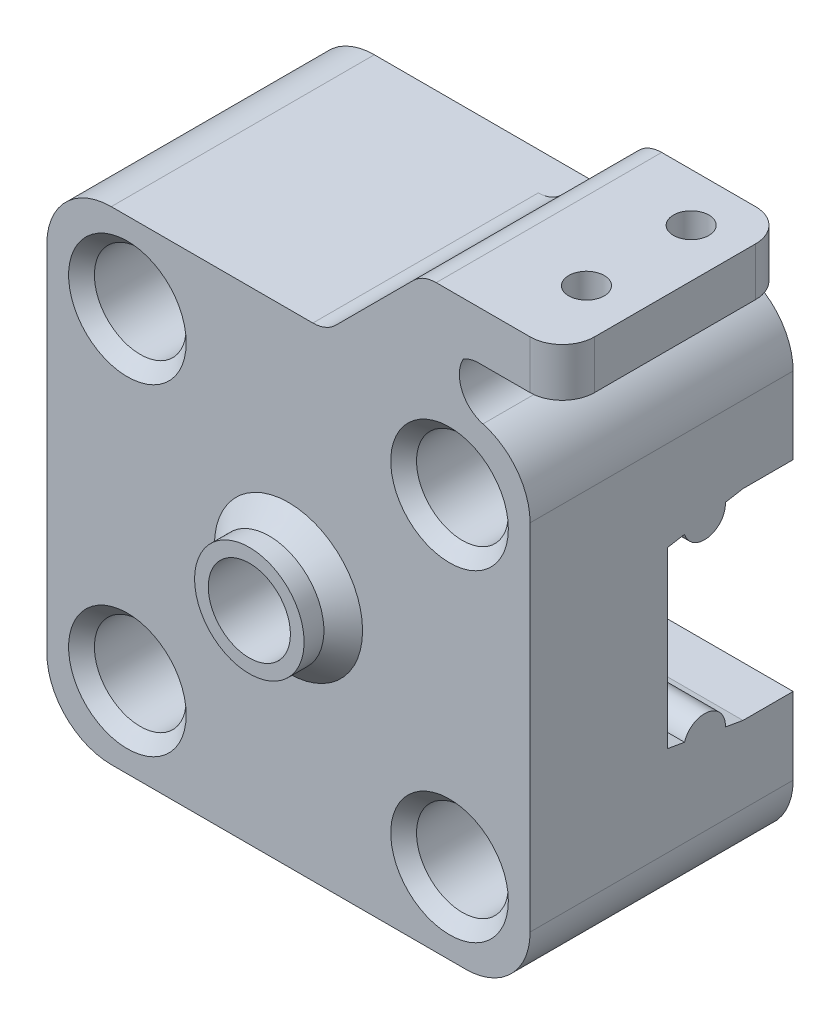
SolidWorks part; units mm, degrees
note: The reader was unsure of these and kept them because the rebuilt part matched: shared geometry of "Sketch1<3>".
ref_plane "Front Plane" through (0, 0, 0) normal (0, 0, 1) x (1, 0, 0)
ref_plane "Top Plane" through (0, 0, 0) normal (0, 1, 0) x (1, 0, 0)
ref_plane "Right Plane" through (0, 0, 0) normal (1, 0, 0) x (0, 0, -1)
sketch "Sketch1" plane through (0, 0, 0) normal (0, 0, 1) x (1, 0, 0)
  line L0 (10, 20) -> (10, 0) construction
  line L1 (0, 0) -> (20, 0) construction
  line L2 (0, 0) -> (0, 20) construction
  line L3 (0, 20) -> (20, 20) construction
  line L4 (20, 0) -> (20, 20) construction
  line L5 (10, 10) -> (68.0208, 10) construction
  line L6 (-5, -5) -> (25, -5)
  line L7 (-5, -5) -> (-5, 25)
  line L8 (-5, 25) -> (25, 25)
  line L9 (25, -5) -> (25, 25)
  line L10 (-5, -5) -> (25, 25) construction
  line L11 (-5, 25) -> (25, -5) construction
  line L13 (25, 16) -> (106.01, 16)
  line L14 (25, 16) -> (25, 4)
  line L15 (25, 4) -> (106.01, 4)
  line L16 (106.01, 16) -> (106.01, 4)
  circle A0 centre (0, 0) radius 1.6
  circle A1 centre (0, 20) radius 1.6
  circle A2 centre (20, 20) radius 1.6
  circle A3 centre (20, 0) radius 1.6
  point P11 (10, 10)
  dimension "D2" = 3.2
  dimension "D1" = 20
  dimension "D3" = 30
  dimension "D4" = 30
  dimension "D5" = 12
  dimension "D6" = 6
  dimension "D7" = 81.01
extrude "Boss-Extrude1" add sketch "Sketch1" along normal blind 6 contours L6 L9 L8 L7 A3 A2 A1 A0 | L16 L13 L9 L15
extrude "Boss-Extrude2" add sketch "Sketch1<3>" along normal blind 22.33 contours L6 L9 L8 L7 A3 A2 A1 A0
sketch "Sketch1<3>" plane through (0, 0, 0) normal (0, 0, 1) x (1, 0, 0) same geometry as "Sketch1"
sketch "Sketch2" plane through (25, 0, 0) normal (1, 0, 0) x (0, 0, -1)
  line L0 (-6.5176, 16.2291) -> (-9.1132, 16.2291)
  line L1 (-9.1132, 16.2291) -> (-10.2051, 16.0365)
  line L2 (-12.742, 15.5892) -> (-13.7853, 15.4053)
  line L3 (-13.7853, 15.4053) -> (-13.7853, 4.594)
  line L4 (-13.7853, 4.594) -> (-12.742, 4.41)
  line L5 (-10.2051, 3.9627) -> (-9.1132, 3.7702)
  line L6 (-9.1132, 3.7702) -> (-6.5176, 3.7702)
  line L7 (-6.5176, 3.7702) -> (-5.9631, 3.7702)
  line L9 (-5.9631, 16.2291) -> (-6.5176, 16.2291)
  line L11 (-22.33, -5) -> (0, -5) construction
  line L12 (-22.33, -5) -> (-22.33, 25) construction
  line L13 (-5.9631, 16.2291) -> (-5.9631, 3.7702)
  arc A0 (-12.742, 15.5892) -> (-10.2051, 16.0365) centre (-11.5012, 15.9695) ccw
  arc A1 (-10.2051, 3.9627) -> (-12.742, 4.41) centre (-11.5012, 4.0298) ccw
extrude "Cut-Extrude1" cut sketch "Sketch2" against normal through all
sketch "Sketch3" plane through (0, 0, 22.33) normal (0, 0, 1) x (1, 0, 0)
  line L0 (-5, 10) -> (25, 10) construction
  line L1 (-5, -5) -> (-5, 25) construction
  line L2 (25, -5) -> (25, 25) construction
  line L3 (10, -5) -> (10, 25) construction
  line L4 (-5, -5) -> (25, -5) construction
  line L5 (-5, 25) -> (25, 25) construction
  circle A0 centre (10, 10) radius 2.55
  dimension "D1" = 5.1
extrude "Cut-Extrude2" cut sketch "Sketch3" against normal blind 8
sketch "Sketch5" plane through (0, 0, 13.7853) normal (0, 0, -1) x (-1, 0, 0)
  line L1 (-5.3235, 10) -> (-7.6617, 14.05)
  line L2 (-7.6617, 14.05) -> (-12.3383, 14.05)
  line L3 (-12.3383, 14.05) -> (-14.6765, 10)
  line L4 (-14.6765, 10) -> (-12.3383, 5.95)
  line L5 (-12.3383, 5.95) -> (-7.6617, 5.95)
  line L6 (-7.6617, 5.95) -> (-5.3235, 10)
  line L8 (-25, 15.4053) -> (-25, 4.594)
  line L9 (-25, 4.594) -> (5, 4.594)
  line L10 (5, 4.594) -> (5, 15.4053)
  line L11 (5, 15.4053) -> (-25, 15.4053)
  line L12 (-25, 15.4053) -> (-25, 4.594)
  line L13 (-25, 4.594) -> (5, 4.594)
  line L15 (5, 15.4053) -> (-25, 15.4053)
  line L18 (5, 4.594) -> (5, 15.4053)
  circle A0 centre (-10, 10) radius 4.05
  circle A1 centre (-10, 10) radius 4.05 construction
  dimension "D2" = 8.1
  dimension "D3" = 8.1
  dimension "D1" = 0
extrude "Cut-Extrude3" cut sketch "Sketch5" against normal blind 4.5
sketch "Sketch6" plane through (0, 0, 0) normal (0, 0, -1) x (-1, 0, 0)
  line L0 (-20, 0) -> (0, 20) construction
  line L1 (0, 20) -> (0, 0) construction
  line L2 (0, 0) -> (-20, 20) construction
  circle A0 centre (-10, 10) radius 5
  dimension "D1" = 10
extrude "Cut-Extrude5" cut sketch "Sketch6" against normal blind 8.6
sketch "Sketch7" plane through (0, 0, 0) normal (0, 0, -1) x (-1, 0, 0)
  line L1 (5, -5) -> (-3.5, -5)
  line L2 (5, -5) -> (5, 25)
  line L3 (5, 25) -> (-3.5, 25)
  line L4 (-3.5, -5) -> (-3.5, 25)
  line L5 (5, 25) -> (-25, 25) construction
  line L6 (-106.01, 10) -> (-3.5, 10) construction
  line L7 (-106.01, 16) -> (-106.01, 4) construction
  line L8 (-3.5, 10) -> (-3.5, 16)
  line L9 (-25, 4) -> (-106.01, 4) construction
  line L10 (-3.5, 16) -> (-65, 16)
  line L11 (-3.5, 16) -> (-3.5, 4)
  line L12 (-3.5, 4) -> (-65, 4)
  line L13 (-65, 16) -> (-65, 4)
  circle A0 centre (-49.5, 10) radius 1.6
  circle A1 centre (-74.5, 10) radius 1.6
  circle A2 centre (-99.5, 10) radius 1.6
  dimension "D4" = 46
  dimension "D5" = 25
  dimension "D6" = 3.2
  dimension "D7" = 3.2
  dimension "D1" = 30
  dimension "D2" = 8.5
  dimension "D3" = 6
  dimension "D8" = 25
extrude "Cut-Extrude6" cut sketch "Sketch7" against normal through all contours L6 A2 | A2 L6 | A1 | A0
sketch "Sketch8" plane through (0, 0, 22.33) normal (0, 0, 1) x (1, 0, 0)
  circle A0 centre (20, 20) radius 2.85
  circle A1 centre (20, 0) radius 2.85
  circle A2 centre (0, 0) radius 2.85
  circle A3 centre (0, 20) radius 2.85
  dimension "D4" = 5.7
extrude "Cut-Extrude7" cut sketch "Sketch8" against normal blind 11
sketch "Sketch9" plane through (0, 0, 22.33) normal (0, 0, 1) x (1, 0, 0)
  circle A0 centre (10, 10) radius 2.55
  circle A1 centre (10, 10) radius 3.4
  dimension "D1" = 5.1
  dimension "D2" = 6.8
extrude "Boss-Extrude3" add sketch "Sketch9" along normal blind 2.43
chamfer "Chamfer1" distance 1.2 angle 45 1 edges at (13.4, 10, 22.33)
fillet "Fillet3" radius 4 8 edges at (25, 4, 2.9815) (25, 16, 2.9815) (25, 25, 11.165) (-5, 25, 11.165) (-5, -5, 11.165) (25, -5, 11.165) (106.01, 4, 3) (106.01, 16, 3)
chamfer "Chamfer2" distance 0.8 angle 45 4 edges at (22.85, 0, 22.33) (2.85, 0, 22.33) (2.85, 20, 22.33) (22.85, 20, 22.33)
sketch "Sketch10" plane through (0, 0, 0) normal (0, 0, -1) x (-1, 0, 0)
  line L1 (-97.8834, 12.8) -> (-101.1166, 12.8)
  line L2 (-101.1166, 12.8) -> (-102.7332, 10)
  line L3 (-102.7332, 10) -> (-101.1166, 7.2)
  line L4 (-101.1166, 7.2) -> (-97.8834, 7.2)
  line L5 (-97.8834, 7.2) -> (-96.2668, 10)
  line L6 (-96.2668, 10) -> (-97.8834, 12.8)
  circle A3 centre (-99.5, 10) radius 2.8 construction
  dimension "D1" = 5.6
sketch "Sketch15" plane through (0, 0, 22.33) normal (0, 0, 1) x (1, 0, 0)
  line L0 (12.3431, 25) -> (18.3431, 31)
  line L1 (18.3431, 31) -> (27, 31)
  line L2 (27, 31) -> (27, 28)
  line L3 (27, 28) -> (21, 28)
  line L4 (25, -1) -> (25, 21)
  line L5 (21, 25) -> (-1, 25)
  line L6 (-5, 21) -> (-5, -1)
  line L7 (-1, -5) -> (21, -5)
  line L8 (25, -1) -> (25, 21)
  line L9 (21, 25) -> (-1, 25)
  line L10 (-5, 21) -> (-5, -1)
  line L11 (-1, -5) -> (21, -5)
  line L12 (21, 28) -> (18, 25)
  arc A4 (25, 21) -> (21, 25) centre (21, 21) ccw
  arc A5 (-1, 25) -> (-5, 21) centre (-1, 21) ccw
  arc A6 (-5, -1) -> (-1, -5) centre (-1, -1) ccw
  arc A7 (21, -5) -> (25, -1) centre (21, -1) ccw
  arc A8 (25, 21) -> (21, 25) centre (21, 21) ccw
  arc A9 (-1, 25) -> (-5, 21) centre (-1, 21) ccw
  arc A10 (-5, -1) -> (-1, -5) centre (-1, -1) ccw
  arc A11 (21, -5) -> (25, -1) centre (21, -1) ccw
  dimension "D2" = 3
  dimension "D3" = 3
  dimension "D4" = 4
  dimension "D5" = 3
  dimension "D6" = 45
  dimension "D7" = 6
  dimension "D1" = 0
extrude "Boss-Extrude6" add sketch "Sketch15" against normal blind 14 contours L12 L3 L2 L1 L0 L9
sketch "Sketch17" plane through (0, 31, 0) normal (0, 1, 0) x (1, 0, 0)
  line L0 (27, -8.33) -> (27, -22.33) construction
  line L1 (18.3431, -8.33) -> (27, -8.33) construction
  circle A0 centre (24, -11.33) radius 1.1
  circle A1 centre (24, -17.83) radius 1.1
  dimension "D1" = 2.2
  dimension "D2" = 6.5
  dimension "D3" = 3
  dimension "D4" = 3
  dimension "D5" = 3
extrude "Cut-Extrude10" cut sketch "Sketch17" against normal up to next
fillet "Fillet5" radius 2 6 edges at (21, 28, 15.33) (27, 29.5, 22.33) (27, 29.5, 8.33) (18.3431, 31, 15.33) (12.3431, 25, 15.33) (18, 25, 15.33)
extrude "Cut-Extrude11" cut sketch "Sketch10" against normal blind 3
chamfer "Chamfer3" distance 0.8 angle 45 6 edges at (101.9249, 8.6, 0) (99.5, 7.2, 0) (97.0751, 8.6, 0) (101.9249, 11.4, 0) (97.0751, 11.4, 0) (99.5, 12.8, 0)
pattern_linear "LPattern2" count 3 spacing 25 along (-1, 0, 0) of "Chamfer3", "Cut-Extrude11"
sketch "Sketch18" plane through (0, 0, 0) normal (0, 0, -1) x (-1, 0, 0)
  line L1 (8.7382, 26.693) -> (-113.4369, 26.693)
  line L2 (8.7382, 26.693) -> (8.7382, -9.0765)
  line L3 (8.7382, -9.0765) -> (-113.4369, -9.0765)
  line L4 (-113.4369, 26.693) -> (-113.4369, -9.0765)
extrude "Cut-Extrude12" cut sketch "Sketch18" against normal blind 6
